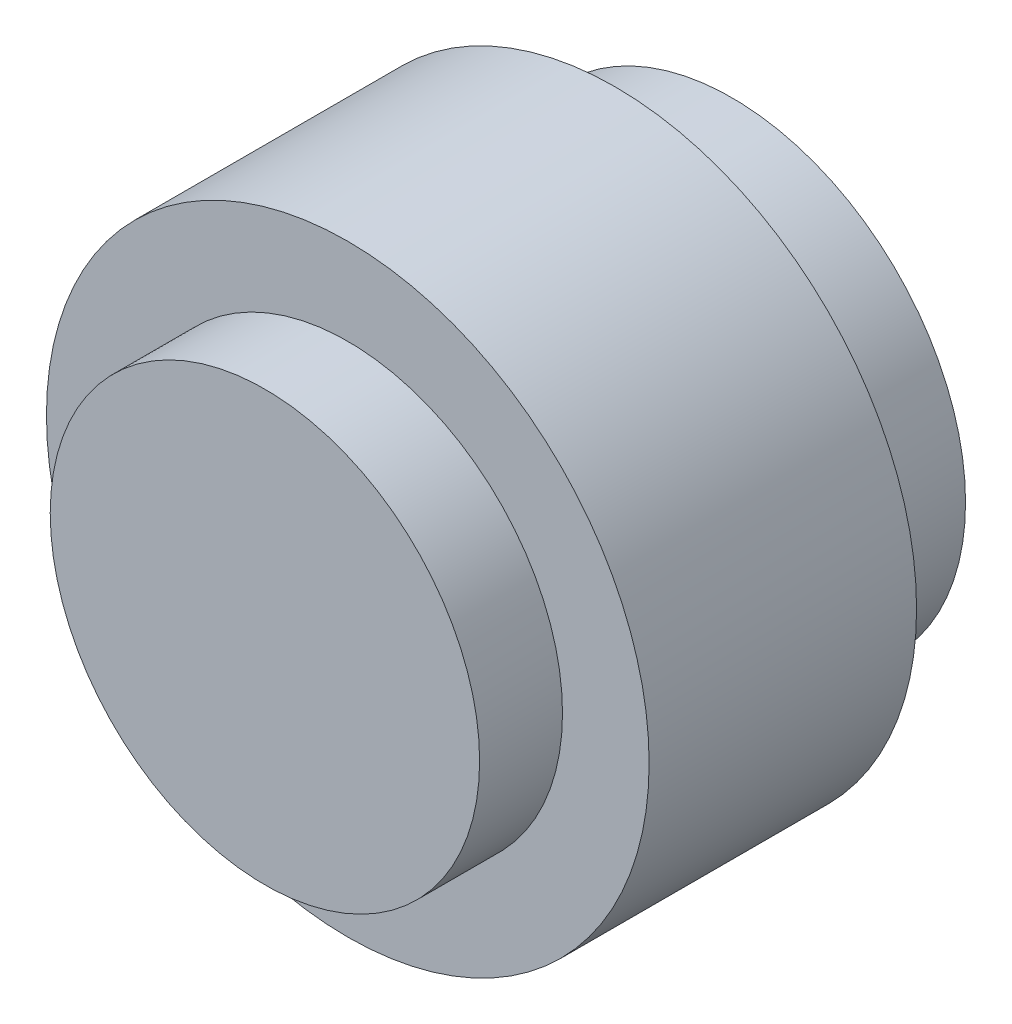
SolidWorks part; units mm, degrees
ref_plane "Front Plane" through (0, 0, 0) normal (0, 0, 1) x (1, 0, 0)
ref_plane "Top Plane" through (0, 0, 0) normal (0, 1, 0) x (1, 0, 0)
ref_plane "Right Plane" through (0, 0, 0) normal (1, 0, 0) x (0, 0, -1)
sketch "Sketch1" plane through (0, 0, 0) normal (0, 0, 1) x (1, 0, 0)
  circle A0 centre (0, 0) radius 40
  circle A1 centre (0, 0) radius 28.5
  circle A2 centre (0, 0) radius 21
  dimension "D1" = 80
  dimension "D2" = 57
  dimension "D3" = 42
extrude "Boss-Extrude1" add sketch "Sketch1" along normal blind 11 contours A1 A2 | A2 region at (-27.6939, 0, 0) region at (0, 0, 0)
extrude "Boss-Extrude2" add sketch "Sketch1<3>" against normal blind 35.5 contours A0 A1 | A1 A2 region at (-38.8686, 0, 0) region at (-27.6939, 0, 0)
sketch "Sketch1<3>" plane through (0, 0, 0) normal (0, 0, 1) x (1, 0, 0) same geometry as "Sketch1"
ref_plane "Plane1" through (0, 0, -35.5) normal (0, 0, -1) x (-1, 0, 0)
sketch "Sketch2" plane through (0, 0, -35.5) normal (0, 0, -1) x (-1, 0, 0)
  line L0 (0, 0) -> (0, 52.4537) construction
  circle A0 centre (0, 37) radius 1.5
  circle A1 centre (26.163, 26.163) radius 1.5
  circle A2 centre (37, 0) radius 1.5
  circle A3 centre (26.163, -26.163) radius 1.5
  circle A4 centre (0, -37) radius 1.5
  circle A5 centre (-26.163, -26.163) radius 1.5
  circle A6 centre (-37, 0) radius 1.5
  circle A7 centre (-26.163, 26.163) radius 1.5
  point P3 (0, 37)
  point P22 (0, 0)
  dimension "D2" = 3
  dimension "D1" = 37
  dimension "D3" = 8
hole_wizard "M3 Tapped Hole1" positions "Sketch3" profile "Sketch4" tap size "M3" standard "ISO"
sketch "Sketch3" plane through (0, 0, -35.5) normal (0, 0, -1) x (-1, 0, 0)
  point P0 (0, 37)
  point P3 (26.163, 26.163)
  point P6 (37, 0)
  point P9 (26.163, -26.163)
  point P12 (0, -37)
  point P15 (-26.163, -26.163)
  point P18 (-37, 0)
  point P21 (-26.163, 26.163)
sketch "Sketch4" plane through (0, 37, -35.5) normal (1, 0, 0) x (0, 1, 0)
  line L0 (0, 0) -> (0, 5.7511)
  line L1 (0, 5.7511) -> (1.25, 5)
  line L2 (1.25, 5) -> (1.25, 0.275)
  line L3 (1.25, 0.275) -> (1.525, 0)
  line L5 (1.525, 0) -> (0, 0)
  line L6 (-1.25, 0.275) -> (-1.525, 0) construction
  line L10 (0, 5.7511) -> (-1.25, 5) construction
  line L11 (0, -6.35) -> (0, 107.95) construction
  dimension "Tap Drill Dia." = 2.5
  dimension "Tap Drill Depth" = 5
  dimension "Near C'Sink Dia." = 3.05
  dimension "Near C'Sink Angle" = 90
  dimension "Drill Angle" = 118
cosmetic thread "Hole Thread1" parameters "D1"=3.5, "D2"=3
cosmetic thread "Hole Thread2" parameters "D1"=3.5, "D2"=3
cosmetic thread "Hole Thread3" parameters "D1"=3.5, "D2"=3
cosmetic thread "Hole Thread4" parameters "D1"=3.5, "D2"=3
cosmetic thread "Hole Thread5" parameters "D1"=3.5, "D2"=3
cosmetic thread "Hole Thread6" parameters "D1"=3.5, "D2"=3
cosmetic thread "Hole Thread7" parameters "D1"=3.5, "D2"=3
cosmetic thread "Hole Thread8" parameters "D1"=3.5, "D2"=3
ref_plane "Plane2" through (0, 0, -35.5) normal (0, 0, -1) x (-1, 0, 0)
sketch "Sketch5" plane through (0, 0, -35.5) normal (0, 0, -1) x (-1, 0, 0)
  circle A0 centre (0, 0) radius 21
  circle A1 centre (0, 0) radius 31
  dimension "D1" = 62
extrude "Boss-Extrude3" add sketch "Sketch5" along normal blind 15.5
